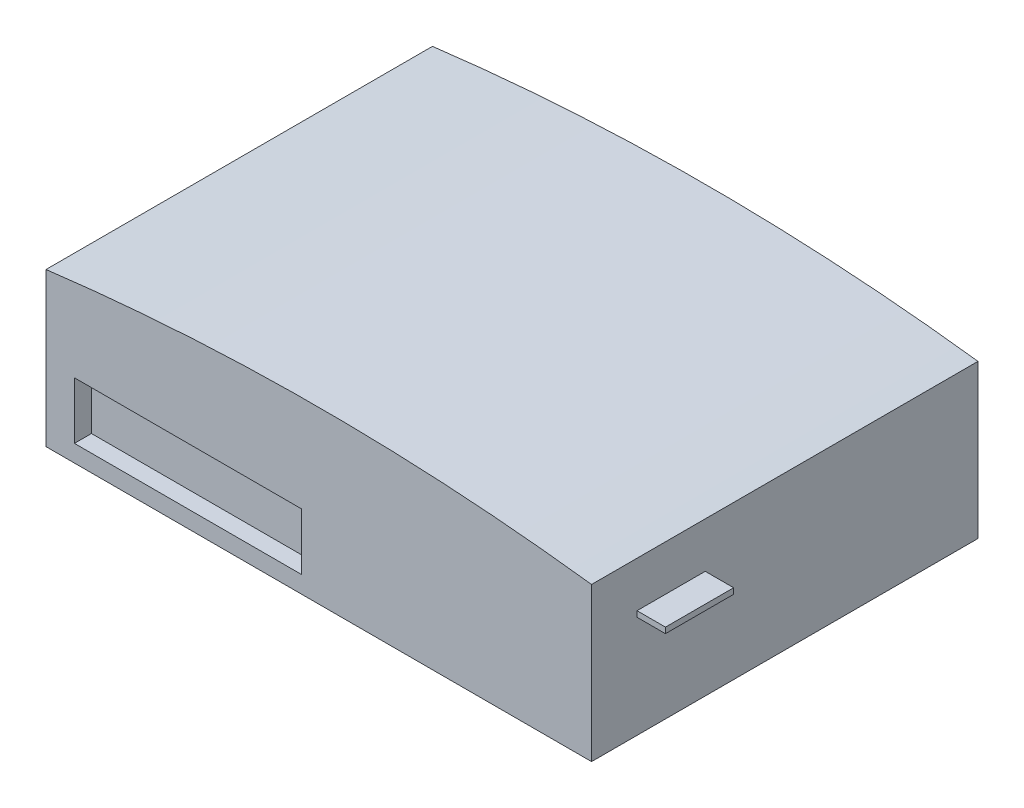
SolidWorks part; units mm, degrees
ref_plane "Front Plane" through (0, 0, 0) normal (0, 0, 1) x (1, 0, 0)
ref_plane "Top Plane" through (0, 0, 0) normal (0, 1, 0) x (1, 0, 0)
ref_plane "Right Plane" through (0, 0, 0) normal (1, 0, 0) x (0, 0, -1)
sketch "Sketch1" plane through (0, 0, 0) normal (0, 1, 0) x (1, 0, 0)
  line L1 (-48, -34) -> (48, -34)
  line L2 (-48, -34) -> (-48, 34)
  line L3 (-48, 34) -> (48, 34)
  line L4 (48, -34) -> (48, 34)
  line L5 (-48, -34) -> (48, 34) construction
  line L6 (-48, 34) -> (48, -34) construction
  point P0 (0, 0)
  dimension "D1" = 68
  dimension "D2" = 96
extrude "Boss-Extrude1" add sketch "Sketch1" along normal blind 30
sketch "Sketch2" plane through (0, 0, 34) normal (0, 0, 1) x (1, 0, 0)
  line L0 (-48, 30) -> (-48, 0) construction
  line L1 (48, 30) -> (48, 0) construction
  line L2 (-48, 30) -> (48, 30) construction
  line L3 (-48, 27) -> (48, 27) construction
  line L4 (-48, 27) -> (-48, 41.3487)
  line L5 (-48, 41.3487) -> (48, 41.3487)
  line L6 (48, 41.3487) -> (48, 27)
  arc A0 (-48, 27) -> (48, 27) centre (0, -355.5) cw
  dimension "D1" = 3
extrude "Cut-Extrude1" cut sketch "Sketch2" against normal through all
sketch "Sketch3" plane through (0, 0, 34) normal (0, 0, 1) x (1, 0, 0)
  line L0 (-48, 0) -> (48, 0) construction
  line L1 (-43, 13) -> (-3, 13)
  line L2 (-43, 13) -> (-43, 3)
  line L3 (-43, 3) -> (-3, 3)
  line L4 (-3, 13) -> (-3, 3)
  line L5 (-48, 27) -> (-48, 0) construction
  dimension "D1" = 3
  dimension "D2" = 5
  dimension "D3" = 10
  dimension "D4" = 40
extrude "Cut-Extrude2" cut sketch "Sketch3" against normal blind 3
sketch "Sketch4" plane through (48, 0, 0) normal (1, 0, 0) x (0, 0, -1)
  line L0 (-34, 27) -> (-34, 0) construction
  line L1 (-26, 19) -> (-14, 19)
  line L2 (-26, 19) -> (-26, 18)
  line L3 (-26, 18) -> (-14, 18)
  line L4 (-14, 19) -> (-14, 18)
  line L5 (-34, 0) -> (34, 0) construction
  dimension "D1" = 12
  dimension "D2" = 8
  dimension "D3" = 18
  dimension "D4" = 1
extrude "Boss-Extrude2" add sketch "Sketch4" along normal blind 5
sketch "Sketch5" plane through (0, 0, 0) normal (0, -1, 0) x (1, 0, 0)
  line L0 (-38, 34) -> (-38, -34) construction
  line L1 (-48, 34) -> (48, 34) construction
  line L2 (48, -34) -> (-48, -34) construction
  line L3 (20, 34) -> (20, -34) construction
  line L4 (-48, 24) -> (48, 24) construction
  line L5 (-48, -34) -> (-48, 34) construction
  line L6 (48, 34) -> (48, -34) construction
  line L7 (-48, -25) -> (48, -25) construction
  circle A0 centre (-38, 24) radius 2.8
  circle A1 centre (-38, 24) radius 1.5
  circle A2 centre (20, 24) radius 2.8
  circle A3 centre (20, 24) radius 1.5
  circle A4 centre (20, -25) radius 2.8
  circle A5 centre (20, -25) radius 1.5
  circle A6 centre (-38, -25) radius 2.8
  circle A7 centre (-38, -25) radius 1.5
  dimension "D6" = 5.6
  dimension "D7" = 3
  dimension "D1" = 10
  dimension "D2" = 10
  dimension "D3" = 58
  dimension "D4" = 49
  dimension "D5" = 9
extrude "Cut-Extrude3" cut sketch "Sketch5" against normal blind 2.2
extrude "Cut-Extrude4" cut sketch "Sketch5<2>" against normal blind 10 contours A1 | A3 | A7 | A5 region at (-38, 0, 24) region at (20, 0, 24) region at (20, 0, -25) region at (-38, 0, -25)
sketch "Sketch5<2>" plane through (0, 0, 0) normal (0, -1, 0) x (1, 0, 0) same geometry as "Sketch5"
